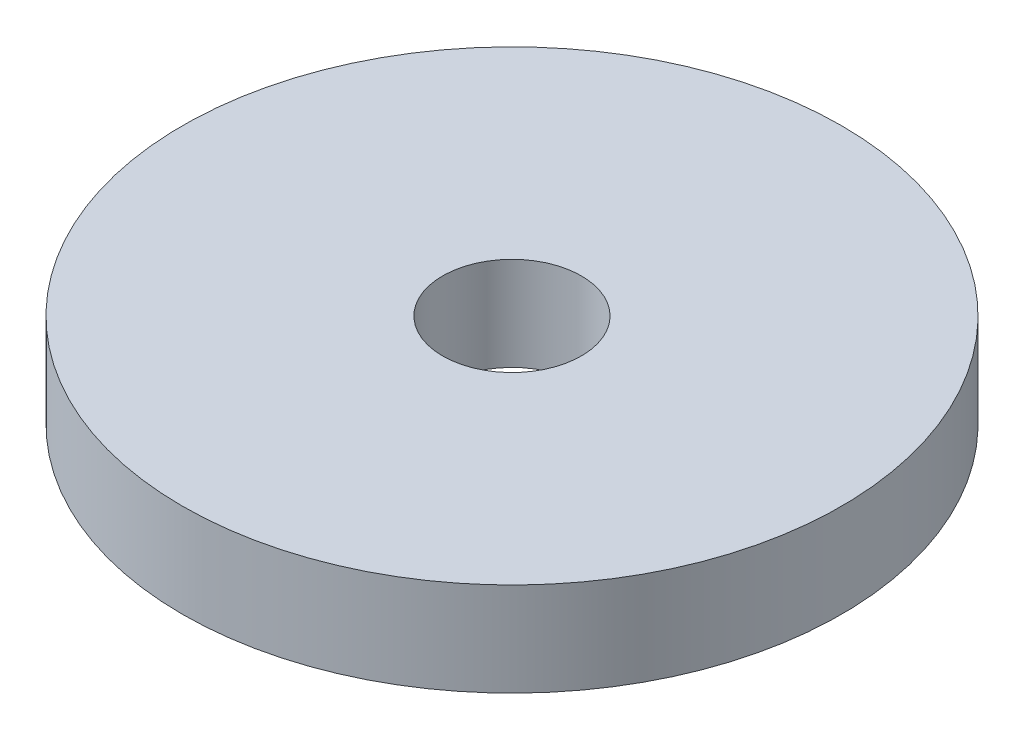
SolidWorks part; units mm, degrees
ref_plane "Front Plane" through (0, 0, 0) normal (0, 0, 1) x (1, 0, 0)
ref_plane "Top Plane" through (0, 0, 0) normal (0, 1, 0) x (1, 0, 0)
ref_plane "Right Plane" through (0, 0, 0) normal (1, 0, 0) x (0, 0, -1)
sketch "Sketch1" plane through (0, 0, 0) normal (0, 1, 0) x (1, 0, 0)
  circle A0 centre (0, 0) radius 95
  dimension "FLANGE_OD" = 190
extrude "Boss-Extrude1" add sketch "Sketch1" along normal blind 27
sketch "Sketch2" plane through (0, 0, 0) normal (0, 1, 0) x (1, 0, 0)
  circle A0 centre (0, 0) radius 20
  dimension "BORE_D" = 40
extrude "Cut-Extrude1" cut sketch "Sketch2" along normal through all
sketch "Sketch3" plane through (0, 27, 0) normal (0, 1, 0) x (1, 0, 0)
  circle A0 centre (0, 0) radius 16.5799 construction
  circle A1 centre (-16.5799, 0) radius 3.1878
  dimension "BOLT_D" = 6.3756
  dimension "BOLT_PCD" = 33.1598
extrude "Cut-Extrude2" cut sketch "Sketch3" against normal blind 17.6756 rebuild error yes
pattern_circular "CirPattern1" count 8 over 360 rebuild error yes
